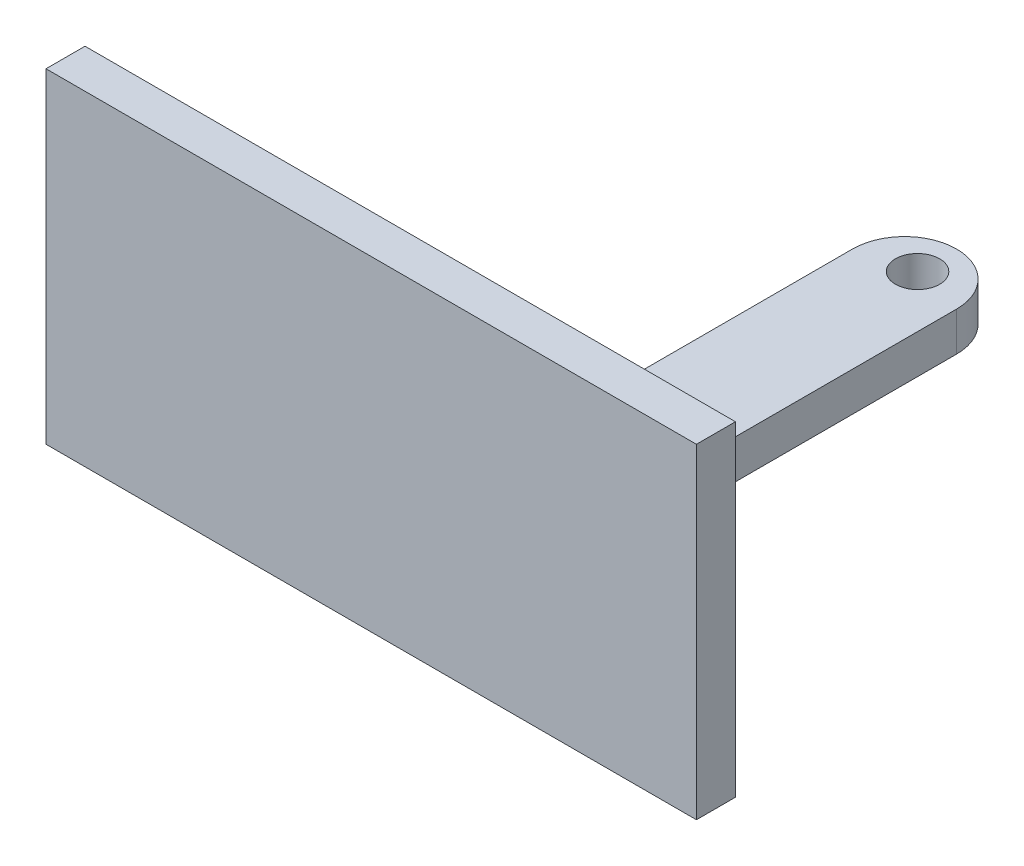
SolidWorks part; units mm, degrees
ref_plane "前视基准面" through (0, 0, 0) normal (0, 0, 1) x (1, 0, 0)
ref_plane "上视基准面" through (0, 0, 0) normal (0, 1, 0) x (1, 0, 0)
ref_plane "右视基准面" through (0, 0, 0) normal (1, 0, 0) x (0, 0, -1)
sketch "Sketch1" plane through (0, 0, 0) normal (0, 0, 1) x (1, 0, 0)
  line L1 (0, 0) -> (50, 0)
  line L2 (0, 0) -> (0, -25)
  line L3 (0, -25) -> (50, -25)
  line L4 (50, 0) -> (50, -25)
  dimension "D1" = 50
  dimension "D2" = 25
extrude "Boss-Extrude1" add sketch "Sketch1" against normal blind 3
sketch "Sketch2" plane through (0, 0, -3) normal (0, 0, -1) x (-1, 0, 0)
  line L0 (-25, -22) -> (-25, 0) construction
  line L1 (0, -25) -> (-50, -25) construction
  line L2 (-50, 0) -> (0, 0) construction
  line L4 (-25, -25) -> (-29, -25)
  line L6 (-25, -22) -> (-29, -22)
  line L7 (-29, -25) -> (-29, -22)
  line L8 (-25, -25) -> (-21, -25)
  line L10 (-25, -22) -> (-21, -22)
  line L11 (-21, -25) -> (-21, -22)
  dimension "D1" = 4
  dimension "D2" = 4
  dimension "D3" = 3
extrude "Boss-Extrude2" add sketch "Sketch2" along normal blind 42
sketch "Sketch3" plane through (0, -22, 0) normal (0, 1, 0) x (1, 0, 0)
  line L0 (25, 45) -> (25, 3) construction
  line L1 (21, 45) -> (29, 45) construction
  line L2 (21, 3) -> (29, 3) construction
  circle A0 centre (25, 42) radius 1.7
  circle A1 centre (25, 15.3) radius 1.7
  dimension "D1" = 3.4
  dimension "D2" = 3
  dimension "D3" = 3.4
  dimension "D4" = 26.7
extrude "Cut-Extrude1" cut sketch "Sketch3" against normal through all
fillet "Fillet2" radius 4 1 edges at (29, -23.5, -45)
fillet "Fillet3" radius 4 1 edges at (21, -23.5, -45)
